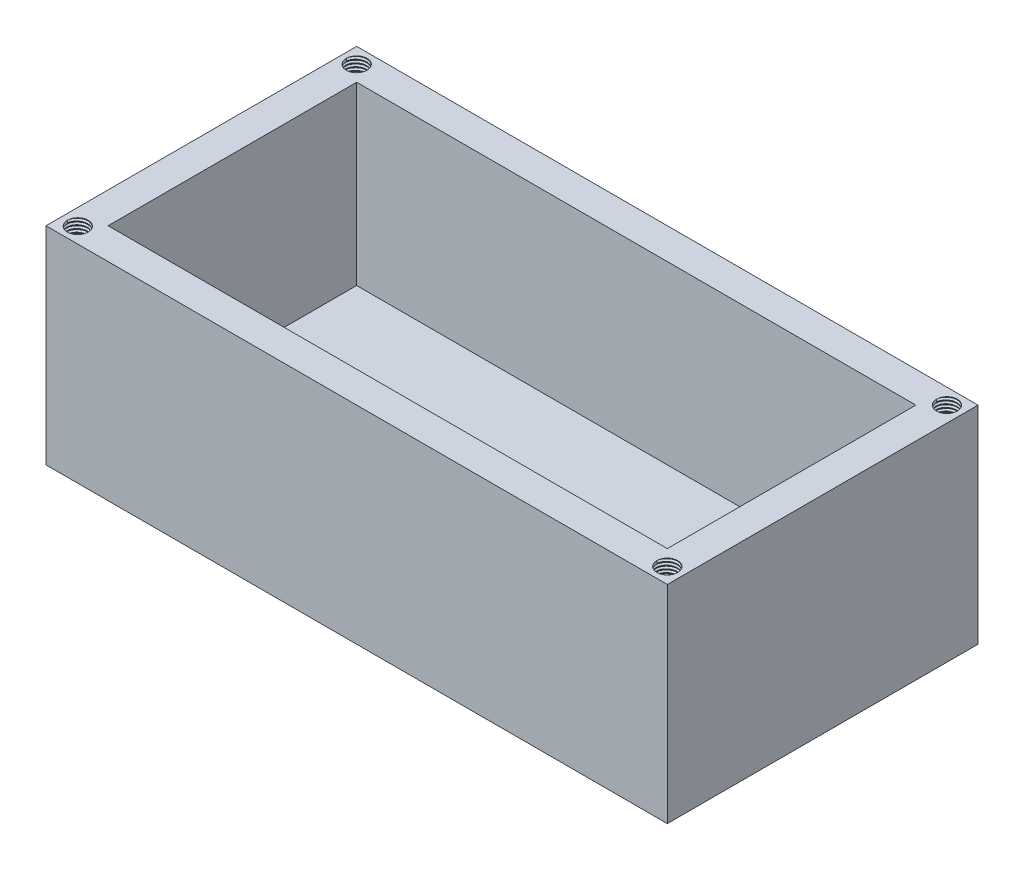
SolidWorks part; units mm, degrees
ref_plane "Front Plane" through (0, 0, 0) normal (0, 0, 1) x (1, 0, 0)
ref_plane "Top Plane" through (0, 0, 0) normal (0, 1, 0) x (1, 0, 0)
ref_plane "Right Plane" through (0, 0, 0) normal (1, 0, 0) x (0, 0, -1)
sketch "Sketch2" plane through (0, 0, 0) normal (0, 1, 0) x (1, 0, 0)
  line L1 (-38.1, 19.05) -> (38.1, 19.05)
  line L2 (-38.1, 19.05) -> (-38.1, -19.05)
  line L3 (-38.1, -19.05) -> (38.1, -19.05)
  line L4 (38.1, 19.05) -> (38.1, -19.05)
  line L5 (-38.1, 19.05) -> (38.1, -19.05) construction
  line L6 (-38.1, -19.05) -> (38.1, 19.05) construction
  point P0 (0, 0)
  dimension "D1" = 76.2
  dimension "D2" = 38.1
extrude "Boss-Extrude1" add sketch "Sketch2" along normal blind 25.4
shell "Shell1" thickness 3.81 removed face at (0, 25.4, 0)
sketch "Sketch3" plane through (0, 3.81, 0) normal (0, 1, 0) x (1, 0, 0)
  circle A0 centre (-12.8336, 0) radius 3.175
  circle A1 centre (4.6289, 0) radius 1.651
  point P4 (0, 0)
  point P5 (0, 0)
  dimension "D1" = 6.35
  dimension "D2" = 3.302
  dimension "D3" = 17.4625
extrude "Cut-Extrude1" cut sketch "Sketch3" against normal up to surface (3.81 mm away) up to face at (0, 0, 0)
sketch "Sketch4" plane through (0, 25.4, 0) normal (0, 1, 0) x (1, 0, 0)
  line L0 (-36.195, 17.145) -> (-36.195, 19.05) construction
  line L1 (38.1, 19.05) -> (-38.1, 19.05) construction
  line L2 (-36.195, 19.05) -> (-36.195, 17.145) construction
  line L3 (-36.195, 17.145) -> (-38.1, 17.145) construction
  line L4 (-38.1, 19.05) -> (-38.1, -19.05) construction
  line L5 (36.195, 17.145) -> (36.195, 19.05) construction
  line L6 (36.195, 19.05) -> (36.195, 17.145) construction
  line L7 (36.195, 17.145) -> (38.1, 17.145) construction
  line L8 (38.1, -19.05) -> (38.1, 19.05) construction
  line L9 (36.195, -17.145) -> (38.1, -17.145) construction
  line L10 (38.1, -17.145) -> (36.195, -17.145) construction
  line L11 (36.195, -17.145) -> (36.195, -19.05) construction
  line L12 (-38.1, -19.05) -> (38.1, -19.05) construction
  line L13 (-36.106, -17.145) -> (-36.106, -19.05) construction
  line L14 (-36.106, -19.05) -> (-36.106, -17.145) construction
  line L15 (-36.106, -17.145) -> (-38.011, -17.145) construction
  circle A0 centre (-36.195, 17.145) radius 1.27
  circle A1 centre (36.195, 17.145) radius 1.27
  circle A2 centre (36.195, -17.145) radius 1.27
  circle A3 centre (-36.106, -17.145) radius 1.27
  point P0 (-36.195, 17.145)
  point P5 (-36.106, -17.145)
  point P9 (36.195, -17.145)
  point P10 (36.195, 17.145)
  point P28 (0, 0)
  dimension "D2" = 2.54
  dimension "D1" = 1.905
extrude "Cut-Extrude2" cut sketch "Sketch4" against normal blind 2.54
thread "Thread1" pitch 0.3969 method cut profile "Thread Profile1" start angle 0, offset 0, length 0, pitch 0.3969, diameter 2.54
ref_plane "Plane1" through (-37.465, 25.4, -17.145) normal (0, 0, 1) x (-1, 0, 0)
sketch "Thread Profile1" plane through (-37.465, 25.4, -17.145) normal (0, 0, 1) x (-1, 0, 0)
  line L0 (0, 0) -> (0, 0.3969) construction
  line L1 (0, 0) -> (0.2148, 0.124)
  line L2 (0.2148, 0.124) -> (0.2148, 0.1736)
  line L3 (0.2148, 0.1736) -> (0, 0.2977)
  line L4 (0.2148, 0.1488) -> (0, 0.1488) construction
  line L11 (0, 0) -> (0, 0.2977)
  point P2 (0, 0)
  dimension "Pitch" = 0.3969
  dimension "Profile_Angle" = 60
  dimension "Profile_Land" = 0.0496
  dimension "Profile_Height" = 0.2148
thread "Thread2" pitch 0.3969 method cut profile "Thread Profile2" start angle 0, offset 0, length 0, pitch 0.3969, diameter 2.54
ref_plane "Plane2" through (-37.376, 25.4, 17.145) normal (0, 0, 1) x (-1, 0, 0)
sketch "Thread Profile2" plane through (-37.376, 25.4, 17.145) normal (0, 0, 1) x (-1, 0, 0)
  line L0 (0, 0) -> (0, 0.3969) construction
  line L1 (0, 0) -> (0.2148, 0.124)
  line L2 (0.2148, 0.124) -> (0.2148, 0.1736)
  line L3 (0.2148, 0.1736) -> (0, 0.2977)
  line L4 (0.2148, 0.1488) -> (0, 0.1488) construction
  line L11 (0, 0) -> (0, 0.2977)
  point P2 (0, 0)
  dimension "Pitch" = 0.3969
  dimension "Profile_Angle" = 60
  dimension "Profile_Land" = 0.0496
  dimension "Profile_Height" = 0.2148
thread "Thread3" pitch 0.3969 method cut profile "Thread Profile3" start angle 0, offset 0, length 0, pitch 0.3969, diameter 2.54
ref_plane "Plane3" through (34.925, 25.4, 17.145) normal (0, 0, 1) x (-1, 0, 0)
sketch "Thread Profile3" plane through (34.925, 25.4, 17.145) normal (0, 0, 1) x (-1, 0, 0)
  line L0 (0, 0) -> (0, 0.3969) construction
  line L1 (0, 0) -> (0.2148, 0.124)
  line L2 (0.2148, 0.124) -> (0.2148, 0.1736)
  line L3 (0.2148, 0.1736) -> (0, 0.2977)
  line L4 (0.2148, 0.1488) -> (0, 0.1488) construction
  line L11 (0, 0) -> (0, 0.2977)
  point P2 (0, 0)
  dimension "Pitch" = 0.3969
  dimension "Profile_Angle" = 60
  dimension "Profile_Land" = 0.0496
  dimension "Profile_Height" = 0.2148
thread "Thread4" pitch 0.3969 method cut profile "Thread Profile4" start angle 0, offset 0, length 0, pitch 0.3969, diameter 2.54
ref_plane "Plane4" through (34.925, 25.4, -17.145) normal (0, 0, 1) x (-1, 0, 0)
sketch "Thread Profile4" plane through (34.925, 25.4, -17.145) normal (0, 0, 1) x (-1, 0, 0)
  line L0 (0, 0) -> (0, 0.3969) construction
  line L1 (0, 0) -> (0.2148, 0.124)
  line L2 (0.2148, 0.124) -> (0.2148, 0.1736)
  line L3 (0.2148, 0.1736) -> (0, 0.2977)
  line L4 (0.2148, 0.1488) -> (0, 0.1488) construction
  line L11 (0, 0) -> (0, 0.2977)
  point P2 (0, 0)
  dimension "Pitch" = 0.3969
  dimension "Profile_Angle" = 60
  dimension "Profile_Land" = 0.0496
  dimension "Profile_Height" = 0.2148
equation "\"GBw\"= 3"
equation "\"GBh\"= 1.5"
equation "\"GBd\"= 1"
equation "\"GBt\"= .15"
equation "\"Din\"= .125"
equation "\"Do\"= .25"
equation "\"GearPD\"= 1"
equation "\"PinionPD\"= .375"
equation "\"TeethC\"= ( \"GearPD\" + \"PinionPD\" ) / 2"
